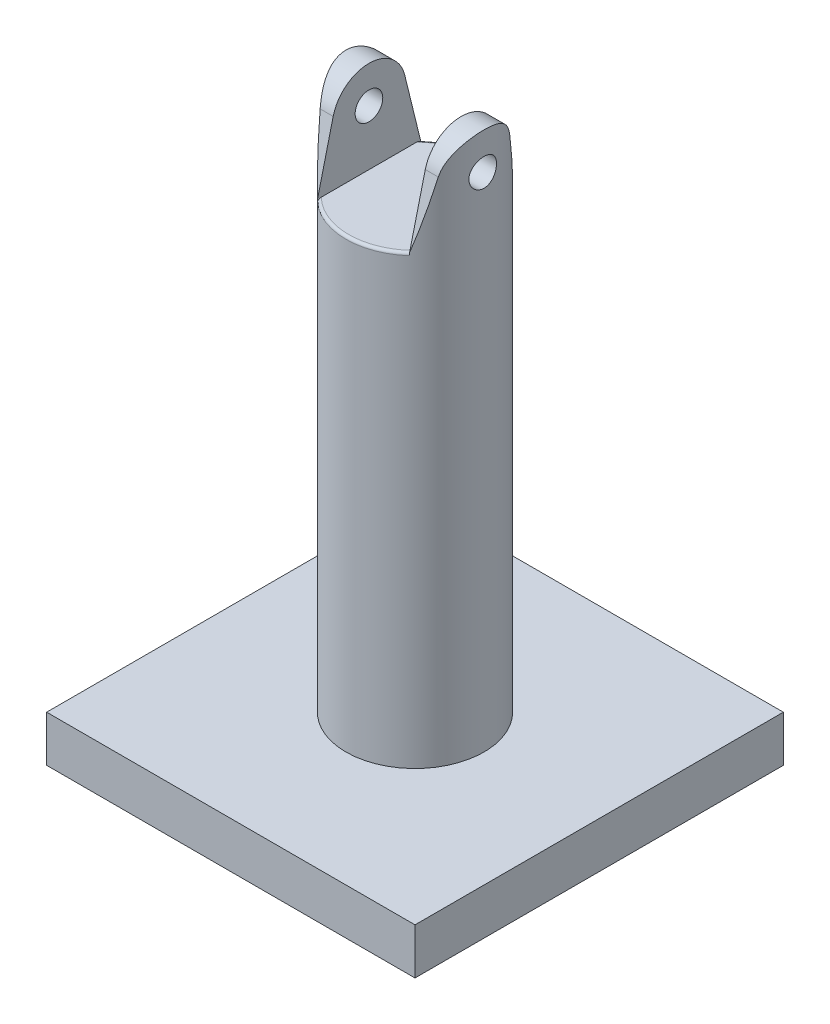
SolidWorks part; units mm, degrees
ref_plane "Alzado" through (0, 0, 0) normal (0, 0, 1) x (1, 0, 0)
ref_plane "Planta" through (0, 0, 0) normal (0, 1, 0) x (1, 0, 0)
ref_plane "Vista lateral" through (0, 0, 0) normal (1, 0, 0) x (0, 0, -1)
sketch "Croquis1" plane through (0, 0, 0) normal (0, 1, 0) x (1, 0, 0)
  circle A0 centre (0, 0) radius 7.5
  dimension "D1" = 15
extrude "Saliente-Extruir1" add sketch "Croquis1" along normal blind 58.52
sketch "Croquis2" plane through (0, 58.52, 0) normal (0, 1, 0) x (1, 0, 0)
  line L1 (-5, 7.9281) -> (5, 7.9281)
  line L2 (-5, 7.9281) -> (-5, -7.9281)
  line L3 (-5, -7.9281) -> (5, -7.9281)
  line L4 (5, 7.9281) -> (5, -7.9281)
  point P4 (0, 7.9281)
  point P6 (5, 0)
  dimension "D1" = 10
extrude "Cortar-Extruir1" cut sketch "Croquis2" against normal blind 10
sketch "Croquis3" plane through (0, 0, 0) normal (1, 0, 0) x (0, 0, -1)
  line L0 (-7.5, 48.52) -> (-5.5902, 48.52)
  line L1 (-5.5902, 48.52) -> (-3.8849, 55.4728)
  line L2 (7.5, 48.52) -> (5.5902, 48.52)
  line L3 (5.5902, 48.52) -> (3.8859, 55.4684)
  line L4 (5.5902, 58.52) -> (-5.5902, 58.52) construction
  arc A0 (-3.8849, 55.4728) -> (3.8859, 55.4684) centre (0, 54.52) cw
  point P11 (0, 0)
  point P14 (0, 58.52)
  point P15 (0, 54.2931)
  point P16 (3.8843, 55.4728)
  point P17 (0, 0)
  point P18 (3.8846, 55.4728)
  point P19 (0, 54.52)
  point P20 (3.8859, 55.4728)
  dimension "D1" = 4
extrude "Cortar-Extruir2" cut sketch "Croquis3" against normal through all both and the other way through all flip side to cut
sketch "Croquis4" plane through (0, 0, 0) normal (1, 0, 0) x (0, 0, -1)
  circle A0 centre (0, 54.52) radius 1.5
  arc A1 (3.8859, 55.4684) -> (-3.8849, 55.4728) centre (0, 54.52) ccw construction
  dimension "D1" = 3
extrude "Cortar-Extruir3" cut sketch "Croquis4" against normal through all both and the other way through all
fillet "Redondeo1" radius 0.3 2 edges at (0, 48.52, -7.5) (0, 48.52, 7.5)
sketch "Croquis6" plane through (0, 0, 0) normal (0, -1, 0) x (1, 0, 0)
  line L1 (-20, 20) -> (20, 20)
  line L2 (-20, 20) -> (-20, -20)
  line L3 (-20, -20) -> (20, -20)
  line L4 (20, 20) -> (20, -20)
  line L5 (-20, 20) -> (20, -20) construction
  line L6 (-20, -20) -> (20, 20) construction
  point P0 (0, 0)
  dimension "D1" = 40
  dimension "D2" = 40
extrude "Saliente-Extruir2" add sketch "Croquis6" along normal blind 5
